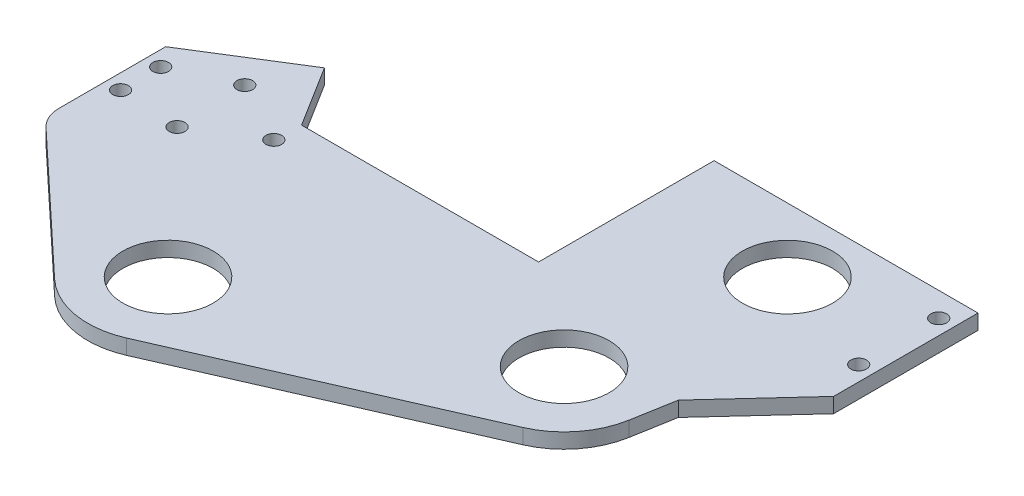
SolidWorks part; units mm, degrees
ref_plane "Front Plane" through (0, 0, 0) normal (0, 0, 1) x (1, 0, 0)
ref_plane "Top Plane" through (0, 0, 0) normal (0, 1, 0) x (1, 0, 0)
ref_plane "Right Plane" through (0, 0, 0) normal (1, 0, 0) x (0, 0, -1)
sketch "Sketch1" plane through (0, 0, 0) normal (0, 1, 0) x (1, 0, 0)
  line L1 (-62.0695, -79.8953) -> (25.163, -41.6958)
  line L5 (39.9361, -22.8907) -> (42.2711, -9.5867)
  line L6 (42.2711, -9.5867) -> (65.827, 16.0128)
  line L12 (-135.7857, -31.9357) -> (-135.7857, 6.1643)
  line L16 (-92.7762, 6.1643) -> (-17.7344, 6.1643)
  line L17 (-135.7857, -31.9357) -> (-89.6201, -75.1681)
  line L19 (65.8268, 61.7268) -> (-17.7344, 61.7268)
  line L20 (65.827, 16.0128) -> (65.8268, 61.7268)
  line L22 (-17.7344, 61.7268) -> (-17.7344, 6.1643)
  line L23 (-135.7857, 6.1643) -> (-104.8539, 25.4927)
  line L24 (-218.6325, 207.5765) -> (-71.6498, -27.6449) construction
  line L25 (-104.8539, 25.4927) -> (-92.7762, 6.1643)
  circle A0 centre (25.8218, 41.4126) radius 14.29
  circle A1 centre (15.0126, -18.5165) radius 14.29
  circle A2 centre (-72.2583, -56.6285) radius 14.29
  arc A4 (39.9361, -22.8907) -> (25.163, -41.6958) centre (15.0127, -18.5164) cw
  arc A6 (-62.0695, -79.8953) -> (-89.6201, -75.1681) centre (-72.2582, -56.6283) cw
  point P11 (-62.0695, -79.8953)
extrude "Boss-Extrude1" add sketch "Sketch1" along normal blind 4.7625
fillet "Fillet1" radius 10 1 edges at (-135.7857, 2.3813, 31.9357)
hole_wizard "#10 Clearance Hole1" positions "Sketch2" profile "Sketch3" hole size "#10" standard "ANSI Inch" end condition through all
sketch "Sketch2" plane through (0, 4.7625, 0) normal (0, 1, 0) x (1, 0, 0)
  point P0 (61.0644, 54.0575)
  point P3 (61.0644, 28.7127)
  point P7 (-131.0232, -0.1857)
  point P10 (-131.0232, -12.8857)
sketch "Sketch3" plane through (61.0644, 4.7625, -54.0575) normal (1, 0, 0) x (0, 0, 1)
  line L0 (0, 0) -> (0, 4.7625)
  line L1 (0, 4.7625) -> (2.4892, 4.7625)
  line L2 (2.4892, 4.7625) -> (2.4892, 0)
  line L5 (2.4892, 0) -> (0, 0)
  line L11 (0, -6.35) -> (0, 107.95) construction
  dimension "Thru Hole Dia." = 4.9784
  dimension "Thru Hole Depth" = 4.7625
sketch "Sketch4" plane through (0, 4.7625, 0) normal (0, 1, 0) x (1, 0, 0)
  line L0 (-72.2583, -56.6285) -> (-102.5432, -8.1625) construction
  line L1 (-102.5432, -8.1625) -> (-93.1193, -2.2738) construction
  line L2 (-102.5432, -8.1625) -> (-111.9672, -14.0512) construction
  line L3 (-102.5432, -8.1625) -> (-112.7324, 8.1436) construction
  line L4 (-102.5432, -8.1625) -> (-186.6679, 126.4651) construction
  dimension "D1" = 57.15
  dimension "D2" = 22.225
hole_wizard "#10 Clearance Hole2" positions "Sketch5" profile "Sketch6" hole size "#10" standard "ANSI Inch" end condition through all
sketch "Sketch5" plane through (0, 4.7625, 0) normal (0, 1, 0) x (1, 0, 0)
  point P0 (-111.9672, -14.0512)
  point P3 (-93.1193, -2.2738)
  point P7 (-112.7324, 8.1436)
sketch "Sketch6" plane through (-111.9672, 4.7625, 14.0512) normal (1, 0, 0) x (0, 0, 1)
  line L0 (0, 0) -> (0, 4.7625)
  line L1 (0, 4.7625) -> (2.4892, 4.7625)
  line L2 (2.4892, 4.7625) -> (2.4892, 0)
  line L5 (2.4892, 0) -> (0, 0)
  line L11 (0, -6.35) -> (0, 107.95) construction
  dimension "Thru Hole Dia." = 4.9784
  dimension "Thru Hole Depth" = 4.7625
